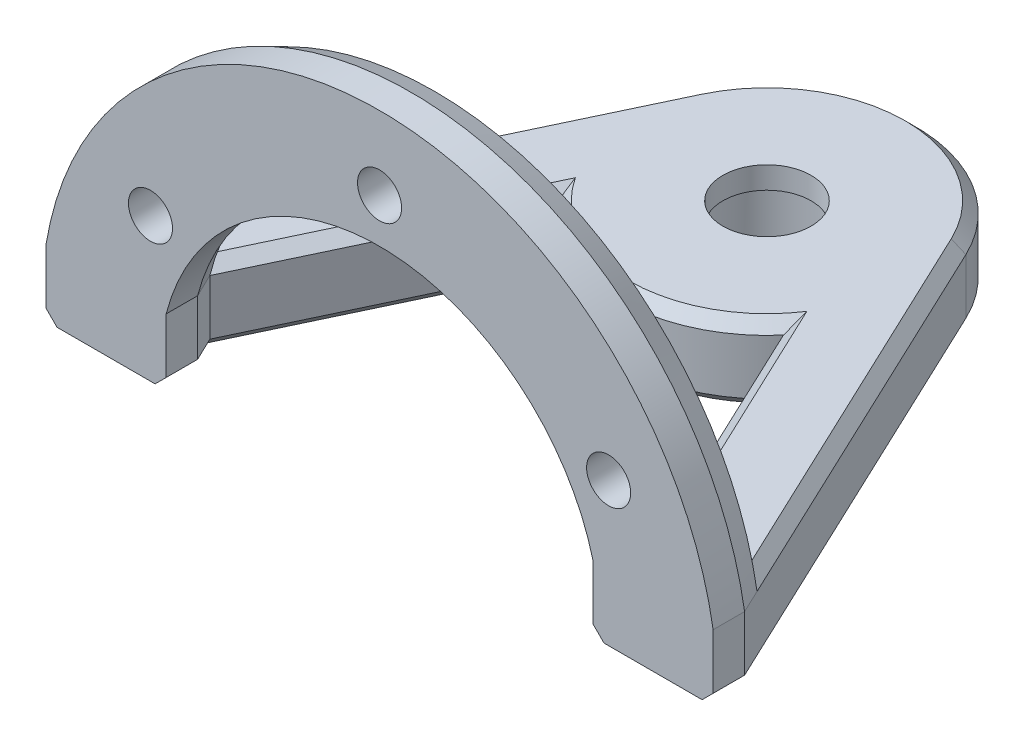
SolidWorks part; units mm, degrees
ref_plane "Front Plane" through (0, 0, 0) normal (0, 0, 1) x (1, 0, 0)
ref_plane "Top Plane" through (0, 0, 0) normal (0, 1, 0) x (1, 0, 0)
ref_plane "Right Plane" through (0, 0, 0) normal (1, 0, 0) x (0, 0, -1)
sketch "Sketch1" plane through (0, 0, 0) normal (0, 0, 1) x (1, 0, 0)
  line L0 (0, 0) -> (0, 24) construction
  line L1 (-30.2648, 5) -> (-19.3649, 5)
  line L2 (19.3649, 5) -> (30.2648, 5)
  circle A3 centre (0, 24) radius 2
  arc A7 (19.3649, 5) -> (-19.3649, 5) centre (0, 0) ccw
  circle A14 centre (0, 0) radius 24 construction
  circle A15 centre (20.7846, 12) radius 2
  circle A19 centre (-20.7846, 12) radius 2
  arc A20 (30.2648, 5) -> (-30.2648, 5) centre (0, 0) ccw
  circle A21 centre (-20.7846, -12) radius 2 [skipped]
  circle A22 centre (0, -24) radius 2 [skipped]
  circle A23 centre (20.7846, -12) radius 2 [skipped]
  point P16 (0, 0)
  dimension "D1" = 48
  dimension "D2" = 40
  dimension "D3" = 4
  dimension "D5" = 61.35
  dimension "D4" = 6
  dimension "D6" = 5
extrude "Boss-Extrude1" add sketch "Sketch1" along normal blind 5
chamfer "Chamfer6" distance 1 angle 65 2 edges at (0, 30.675, 0) (0, 20, 0) first distance on face at (0, 15.1688, 0)
sketch "Sketch4" plane through (0, 5, -5) normal (0, -1, 0) x (-1, 0, 0)
  line L0 (-19.3649, -10) -> (-30.2648, -10) construction
  line L4 (-30.2648, -7.1445) -> (-29.2507, -5) construction
  line L12 (-30.2648, -10) -> (-19.3649, -10)
  line L15 (-30.2648, -7.1445) -> (-30.2648, -10)
  line L16 (0, -2.3789) -> (0, 25.15) construction
  line L17 (-30.2648, -7.1445) -> (-12.2545, 30.9445)
  line L18 (-20.3961, -5) -> (-10.3043, 16.3426)
  line L20 (-30.2648, -10) -> (-30.2648, -7.1445) construction
  line L22 (0, -2.3789) -> (0, 34.8026) construction
  line L23 (0, -10) -> (0, -5) construction
  line L24 (-19.3649, -10) -> (19.3649, -10) construction
  line L25 (20.3961, -5) -> (-20.3961, -5) construction
  line L26 (-19.3649, -10) -> (-19.3649, -7.1445)
  line L27 (-20.3961, -5) -> (-19.3649, -7.1445)
  line L29 (30.2648, -7.1445) -> (29.2507, -5) construction
  line L30 (20.3961, -5) -> (19.3649, -7.1445)
  line L31 (19.3649, -10) -> (19.3649, -7.1445)
  line L32 (20.3961, -5) -> (10.3043, 16.3426)
  line L33 (30.2648, -7.1445) -> (12.2545, 30.9445)
  line L34 (30.2648, -7.1445) -> (30.2648, -10)
  line L35 (30.2648, -10) -> (19.3649, -10)
  circle A0 centre (0, 25.15) radius 5
  arc A1 (-10.3043, 16.3426) -> (10.3043, 16.3426) centre (0, 25.15) ccw
  arc A2 (12.2545, 30.9445) -> (-12.2545, 30.9445) centre (0, 25.15) ccw
  dimension "D1" = 10
  dimension "D3" = 35.15
extrude "Boss-Extrude4" add sketch "Sketch4" along normal blind 6
sketch "Sketch5" plane through (0, 5, 0) normal (0, 1, 0) x (1, 0, 0)
  line L6 (10.3043, 21.3426) -> (20.3961, 0)
  line L7 (20.3961, 0) -> (29.2507, 0)
  line L8 (29.2507, 0) -> (12.2545, 35.9445)
  line L9 (-12.2545, 35.9445) -> (-29.2507, 0)
  line L10 (-29.2507, 0) -> (-20.3961, 0)
  line L11 (-20.3961, 0) -> (-10.3043, 21.3426)
  line L12 (10.3043, 21.3426) -> (20.3961, 0)
  line L13 (20.3961, 0) -> (29.2507, 0)
  line L14 (29.2507, 0) -> (12.2545, 35.9445)
  line L15 (-12.2545, 35.9445) -> (-29.2507, 0)
  line L16 (-29.2507, 0) -> (-20.3961, 0)
  line L17 (-20.3961, 0) -> (-10.3043, 21.3426)
  arc A2 (12.2545, 35.9445) -> (-12.2545, 35.9445) centre (0, 30.15) ccw
  arc A3 (-10.3043, 21.3426) -> (10.3043, 21.3426) centre (0, 30.15) ccw
  arc A4 (12.2545, 35.9445) -> (-12.2545, 35.9445) centre (0, 30.15) ccw
  arc A5 (-10.3043, 21.3426) -> (10.3043, 21.3426) centre (0, 30.15) ccw
  circle A6 centre (0, 30.15) radius 4
  dimension "D2" = 8
  dimension "D1" = 0
extrude "Boss-Extrude5" add sketch "Sketch5" along normal blind 1 and the other way blind 1
chamfer "Chamfer8" distance 1 angle 45 6 edges at (-15.3502, 6, -10.6713) (0, 6, -16.5946) (15.3502, 6, -10.6713) (20.7526, 6, -17.9723) (0, 6, -43.7054) (-20.7526, 6, -17.9723)
chamfer "Chamfer9" distance 1 angle 45 12 edges at (-30.2648, -1, 3.5723) (-21.2596, -1, -16.9) (0, -1, -43.7054) (21.2596, -1, -16.9) (30.2648, -1, 3.5723) (-19.3649, -1, 3.5723) (-19.8805, -1, 1.0723) (19.3649, -1, 3.5723) (19.8805, -1, 1.0723) (-15.3502, -1, -10.6713) (0, -1, -16.5946) (15.3502, -1, -10.6713)
sketch "Sketch6" plane through (0, -1, 0) normal (0, -1, 0) x (1, 0, 0)
  circle A0 centre (0, -30.15) radius 6
  circle A1 centre (0, -30.15) radius 10
  dimension "D1" = 20
  dimension "D2" = 12
extrude "Cut-Extrude1" cut sketch "Sketch6" against normal blind 1
